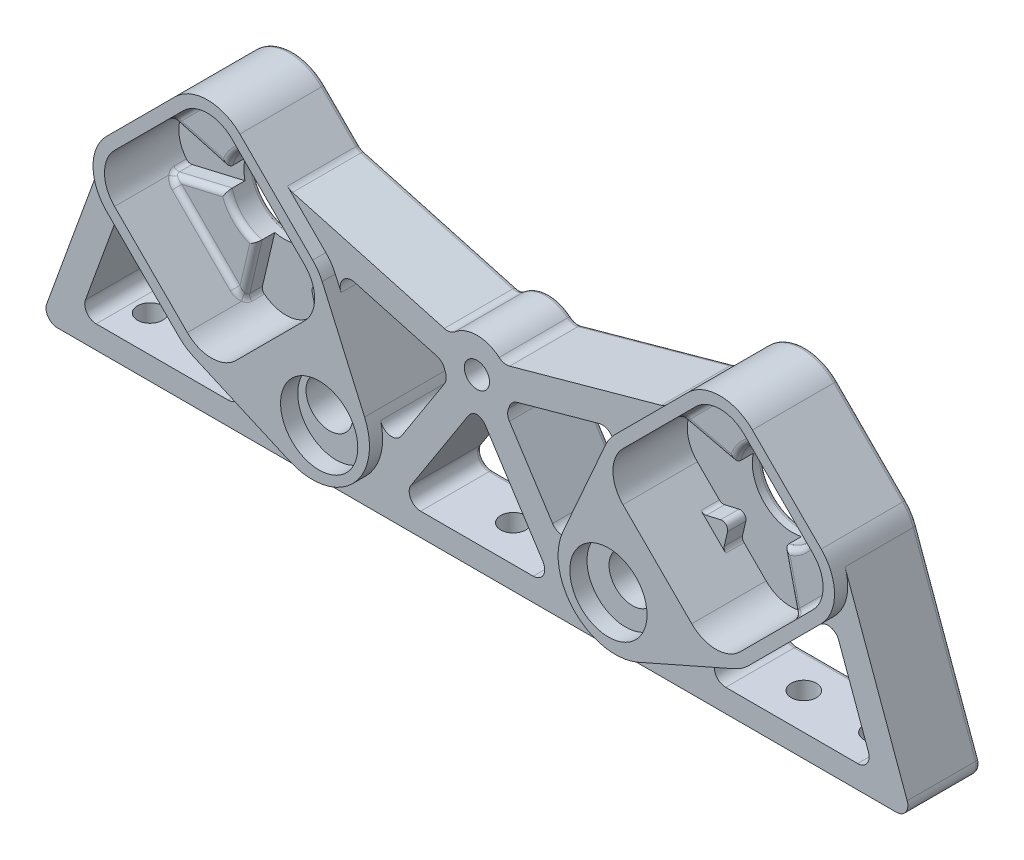
SolidWorks part; units mm, degrees
other "Markup1"
sketch "Sketch10" plane through (13.5539, 56.2954, 15) normal (-0.4315, 0.0322, 0.9016) x (0.8799, -0.2056, 0.4284)
ref_plane "Front Plane" through (0, 0, 0) normal (0, 0, 1) x (1, 0, 0)
ref_plane "Top Plane" through (0, 0, 0) normal (0, 1, 0) x (1, 0, 0)
ref_plane "Right Plane" through (0, 0, 0) normal (1, 0, 0) x (0, 0, -1)
sketch "Sketch1" plane through (0, 0, 0) normal (0, 0, 1) x (1, 0, 0)
  line L0 (0, 0) -> (60.4965, 0) construction
  circle A0 centre (0, 0) radius 25.4 construction
  circle A1 centre (44.45, 35.921) radius 31.75 construction
  circle A2 centre (133.35, 35.921) radius 31.75 construction
  circle A3 centre (177.8, 0) radius 25.4 construction
  circle A4 centre (222.25, 35.921) radius 31.75 construction
  circle A5 centre (311.15, 35.921) radius 31.75 construction
  circle A6 centre (355.6, 0) radius 25.4 construction
  circle A7 centre (0, 0) radius 50.8 construction
  circle A8 centre (355.6, 0) radius 50.8 construction
  circle A9 centre (177.8, 0) radius 50.8 construction
  circle A10 centre (88.9, 35.921) radius 12.7 construction
  circle A11 centre (266.7, 35.921) radius 12.7 construction
  point P20 (-50.8, 0)
  point P21 (406.4, 0)
  dimension "D1" = 50.8
  dimension "D2" = 63.5
  dimension "D4" = 101.6
  dimension "D5" = 25.4
  dimension "D6" = 25.4
  dimension "D3" = 355.6
  dimension "D7" = 177.8
  dimension "D8" = 177.8
  dimension "D9" = 457.2
  dimension "D10" = 44.45
sketch "Sketch2" plane through (0, 0, 0) normal (0, 0, 1) x (1, 0, 0)
  line L0 (-200000, 0) -> (200060.4965, 0) construction
  line L1 (-44.45, 6.35) -> (400.05, 6.35) construction
  line L2 (-44.45, 6.35) -> (-44.45, -19.05) construction
  line L3 (-44.45, -19.05) -> (400.05, -19.05) construction
  line L4 (400.05, 6.35) -> (400.05, -19.05) construction
  circle A0 centre (-38.1, 0) radius 2.25 construction
  circle A2 centre (-31.75, -6.35) radius 2.25 construction
  circle A3 centre (-25.4, 0) radius 2.25 construction
  circle A4 centre (-12.7, 0) radius 2.25 construction
  circle A5 centre (0, 0) radius 2.25 construction
  circle A6 centre (12.7, 0) radius 2.25 construction
  circle A7 centre (25.4, 0) radius 2.25 construction
  circle A8 centre (38.1, 0) radius 2.25 construction
  circle A9 centre (50.8, 0) radius 2.25 construction
  circle A10 centre (63.5, 0) radius 2.25 construction
  circle A11 centre (76.2, 0) radius 2.25 construction
  circle A12 centre (88.9, 0) radius 2.25 construction
  circle A13 centre (101.6, 0) radius 2.25 construction
  circle A14 centre (114.3, 0) radius 2.25 construction
  circle A15 centre (127, 0) radius 2.25 construction
  circle A16 centre (139.7, 0) radius 2.25 construction
  circle A17 centre (152.4, 0) radius 2.25 construction
  circle A18 centre (165.1, 0) radius 2.25 construction
  circle A19 centre (177.8, 0) radius 2.25 construction
  circle A20 centre (190.5, 0) radius 2.25 construction
  circle A21 centre (203.2, 0) radius 2.25 construction
  circle A22 centre (215.9, 0) radius 2.25 construction
  circle A23 centre (228.6, 0) radius 2.25 construction
  circle A24 centre (241.3, 0) radius 2.25 construction
  circle A25 centre (254, 0) radius 2.25 construction
  circle A26 centre (266.7, 0) radius 2.25 construction
  circle A27 centre (279.4, 0) radius 2.25 construction
  circle A28 centre (292.1, 0) radius 2.25 construction
  circle A29 centre (304.8, 0) radius 2.25 construction
  circle A30 centre (317.5, 0) radius 2.25 construction
  circle A31 centre (330.2, 0) radius 2.25 construction
  circle A32 centre (342.9, 0) radius 2.25 construction
  circle A33 centre (355.6, 0) radius 2.25 construction
  circle A34 centre (368.3, 0) radius 2.25 construction
  circle A35 centre (381, 0) radius 2.25 construction
  circle A36 centre (393.7, 0) radius 2.25 construction
  circle A37 centre (-25.4, -12.7) radius 2.25 construction
  circle A38 centre (-12.7, -12.7) radius 2.25 construction
  circle A39 centre (0, -12.7) radius 2.25 construction
  circle A40 centre (12.7, -12.7) radius 2.25 construction
  circle A41 centre (25.4, -12.7) radius 2.25 construction
  circle A42 centre (38.1, -12.7) radius 2.25 construction
  circle A43 centre (50.8, -12.7) radius 2.25 construction
  circle A44 centre (63.5, -12.7) radius 2.25 construction
  circle A45 centre (76.2, -12.7) radius 2.25 construction
  circle A46 centre (88.9, -12.7) radius 2.25 construction
  circle A47 centre (101.6, -12.7) radius 2.25 construction
  circle A48 centre (114.3, -12.7) radius 2.25 construction
  circle A49 centre (127, -12.7) radius 2.25 construction
  circle A50 centre (139.7, -12.7) radius 2.25 construction
  circle A51 centre (152.4, -12.7) radius 2.25 construction
  circle A52 centre (165.1, -12.7) radius 2.25 construction
  circle A53 centre (177.8, -12.7) radius 2.25 construction
  circle A54 centre (190.5, -12.7) radius 2.25 construction
  circle A55 centre (203.2, -12.7) radius 2.25 construction
  circle A56 centre (215.9, -12.7) radius 2.25 construction
  circle A57 centre (228.6, -12.7) radius 2.25 construction
  circle A58 centre (241.3, -12.7) radius 2.25 construction
  circle A59 centre (254, -12.7) radius 2.25 construction
  circle A60 centre (266.7, -12.7) radius 2.25 construction
  circle A61 centre (279.4, -12.7) radius 2.25 construction
  circle A62 centre (292.1, -12.7) radius 2.25 construction
  circle A63 centre (304.8, -12.7) radius 2.25 construction
  circle A64 centre (317.5, -12.7) radius 2.25 construction
  circle A65 centre (330.2, -12.7) radius 2.25 construction
  circle A66 centre (342.9, -12.7) radius 2.25 construction
  circle A67 centre (355.6, -12.7) radius 2.25 construction
  circle A68 centre (368.3, -12.7) radius 2.25 construction
  circle A69 centre (381, -12.7) radius 2.25 construction
  circle A70 centre (393.7, -12.7) radius 2.25 construction
  circle A71 centre (-38.1, -12.7) radius 2.25 construction
  circle A72 centre (-19.05, -6.35) radius 2.25 construction
  circle A73 centre (-6.35, -6.35) radius 2.25 construction
  circle A74 centre (6.35, -6.35) radius 2.25 construction
  circle A75 centre (19.05, -6.35) radius 2.25 construction
  circle A76 centre (31.75, -6.35) radius 2.25 construction
  circle A77 centre (44.45, -6.35) radius 2.25 construction
  circle A78 centre (57.15, -6.35) radius 2.25 construction
  circle A79 centre (69.85, -6.35) radius 2.25 construction
  circle A80 centre (82.55, -6.35) radius 2.25 construction
  circle A81 centre (95.25, -6.35) radius 2.25 construction
  circle A82 centre (107.95, -6.35) radius 2.25 construction
  circle A83 centre (120.65, -6.35) radius 2.25 construction
  circle A84 centre (133.35, -6.35) radius 2.25 construction
  circle A85 centre (146.05, -6.35) radius 2.25 construction
  circle A86 centre (158.75, -6.35) radius 2.25 construction
  circle A87 centre (171.45, -6.35) radius 2.25 construction
  circle A88 centre (184.15, -6.35) radius 2.25 construction
  circle A89 centre (196.85, -6.35) radius 2.25 construction
  circle A90 centre (209.55, -6.35) radius 2.25 construction
  circle A91 centre (222.25, -6.35) radius 2.25 construction
  circle A92 centre (234.95, -6.35) radius 2.25 construction
  circle A93 centre (247.65, -6.35) radius 2.25 construction
  circle A94 centre (260.35, -6.35) radius 2.25 construction
  circle A95 centre (273.05, -6.35) radius 2.25 construction
  circle A96 centre (285.75, -6.35) radius 2.25 construction
  circle A97 centre (298.45, -6.35) radius 2.25 construction
  circle A98 centre (311.15, -6.35) radius 2.25 construction
  circle A99 centre (323.85, -6.35) radius 2.25 construction
  circle A100 centre (336.55, -6.35) radius 2.25 construction
  circle A101 centre (349.25, -6.35) radius 2.25 construction
  circle A102 centre (361.95, -6.35) radius 2.25 construction
  circle A103 centre (374.65, -6.35) radius 2.25 construction
  circle A104 centre (387.35, -6.35) radius 2.25 construction
  dimension "D5" = 4.5
  dimension "D1" = 25.4
  dimension "D2" = 444.5
  dimension "D3" = 6.35
  dimension "D4" = 44.45
  dimension "D6" = 6.35
  dimension "D7" = 6.35
  dimension "D8" = 6.35
  dimension "D12" = 12.7
  dimension "D9" = 35
  dimension "D10" = 2
  dimension "D11" = 34
sketch "Sketch4" plane through (0, 0, 0) normal (0, 0, 1) x (1, 0, 0)
  line L0 (61.067, 39.8101) -> (48.3391, 52.538)
  line L1 (61.067, 31.3248) -> (49.0462, 19.304)
  line L2 (39.8538, 52.538) -> (27.833, 40.5172)
  line L3 (40.5609, 19.304) -> (27.833, 32.0319)
  line L4 (65.3097, 35.5675) -> (23.5903, 36.2746) construction
  line L5 (44.0964, 56.7807) -> (44.8036, 15.0614) construction
  line L6 (44.9803, 59.0788) -> (21.2923, 35.3907) construction
  line L7 (44.45, 35.921) -> (62.4105, 17.9605) construction
  line L8 (62.4105, 17.9605) -> (63.6126, 16.7584) construction
  line L9 (33.1363, 47.2347) -> (74.1485, 6.2225) construction
  line L10 (88.9, 35.921) -> (88.9, 9.7206) construction
  line L11 (44.9803, 59.0788) -> (85.9925, 18.0666) construction
  line L12 (21.2923, 35.3907) -> (62.3044, -5.6215) construction
  line L13 (85.9925, 18.0666) -> (62.3044, -5.6215) construction
  line L14 (132.8197, 59.0788) -> (156.5077, 35.3907) construction
  line L15 (156.5077, 35.3907) -> (115.4956, -5.6215) construction
  line L16 (132.8197, 59.0788) -> (91.8075, 18.0666) construction
  line L17 (91.8075, 18.0666) -> (115.4956, -5.6215) construction
  line L18 (137.9462, 52.538) -> (149.967, 40.5172)
  line L19 (137.2391, 19.304) -> (149.967, 32.0319)
  line L20 (116.733, 31.3248) -> (128.7538, 19.304)
  line L21 (116.733, 39.8101) -> (129.4609, 52.538)
  line L25 (-44.45, 6.35) -> (400.05, 6.35) construction
  circle A0 centre (44.45, 35.921) radius 7
  circle A1 centre (88.9, 35.921) radius 2.2
  arc A3 (61.067, 39.8101) -> (61.067, 31.3248) centre (56.8244, 35.5675) cw
  circle A4 centre (62.4105, 17.9605) radius 4.1
  circle A5 centre (63.6126, 16.7584) radius 6.75
  arc A6 (49.0462, 19.304) -> (40.5609, 19.304) centre (44.8036, 23.5467) cw
  arc A7 (27.833, 32.0319) -> (27.833, 40.5172) centre (32.0756, 36.2746) cw
  arc A8 (39.8538, 52.538) -> (48.3391, 52.538) centre (44.0964, 48.2954) cw
  circle A9 centre (115.3895, 17.9605) radius 4.1
  circle A10 centre (114.1874, 16.7584) radius 6.75
  circle A11 centre (133.35, 35.921) radius 7
  arc A12 (149.967, 32.0319) -> (149.967, 40.5172) centre (145.7244, 36.2746) ccw
  arc A13 (128.7538, 19.304) -> (137.2391, 19.304) centre (132.9964, 23.5467) ccw
  arc A14 (116.733, 39.8101) -> (116.733, 31.3248) centre (120.9756, 35.5675) ccw
  arc A15 (137.9462, 52.538) -> (129.4609, 52.538) centre (133.7036, 48.2954) ccw
  dimension "D1" = 4.4
  dimension "D2" = 14
  dimension "D7" = 13.5
  dimension "D8" = 8.2
  dimension "D9" = 6
  dimension "D3" = 29
  dimension "D4" = 30
  dimension "D5" = 10.4
  dimension "D6" = 1.7
  dimension "D10" = 58
  dimension "D11" = 33.5
  dimension "D12" = 16
  dimension "D13" = 45
sketch "Sketch6" plane through (0, 0, 0) normal (0, 0, 1) x (1, 0, 0)
  line L0 (72.4105, 10.35) -> (105.3895, 10.35)
  line L1 (88.9, 200035.921) -> (88.9, -199990.2794) construction
  line L2 (165.1, 6.35) -> (12.7, 6.35)
  line L3 (-44.45, 6.35) -> (400.05, 6.35) construction
  line L8 (40.5609, 19.304) -> (27.833, 32.0319) construction
  line L9 (61.067, 31.3248) -> (49.0462, 19.304) construction
  line L10 (61.067, 39.8101) -> (48.3391, 52.538) construction
  line L11 (39.8538, 52.538) -> (27.833, 40.5172) construction
  line L12 (40.5609, 19.304) -> (27.833, 32.0319) construction
  line L13 (61.067, 31.3248) -> (49.0462, 19.304) construction
  line L14 (61.067, 39.8101) -> (48.3391, 52.538) construction
  line L15 (62.4812, 41.2243) -> (49.7533, 53.9522)
  line L16 (39.8538, 52.538) -> (27.833, 40.5172) construction
  line L18 (38.4396, 53.9522) -> (26.4188, 41.9314)
  line L21 (39.1467, 17.8898) -> (26.4188, 30.6177)
  line L22 (71.5588, 21.9989) -> (64.143, 38.7982)
  line L23 (41.5728, 16.228) -> (58.3721, 8.8122)
  line L24 (54.8885, 10.35) -> (19.4716, 10.35)
  line L34 (19.4716, 10.35) -> (26.7206, 30.3159)
  line L37 (88.9, 35.921) -> (105.3895, 10.35) construction
  line L38 (12.7, 6.35) -> (24.5559, 39.0048)
  line L39 (88.9, 35.921) -> (44.0964, 48.2954) construction
  line L40 (84.308, 39.7829) -> (56.144, 47.5616)
  line L41 (63.1751, 40.4324) -> (82.9769, 34.9633)
  line L42 (88.9, 35.921) -> (133.7036, 48.2954) construction
  line L43 (137.9462, 52.538) -> (149.967, 40.5172) construction
  line L44 (88.9, 35.921) -> (72.4105, 10.35) construction
  line L45 (116.733, 39.8101) -> (129.4609, 52.538) construction
  line L46 (72.4105, 17.9605) -> (72.4105, 10.35)
  line L47 (72.4105, 14.963) -> (83.843, 32.692)
  line L48 (75.3852, 10.35) -> (88.0451, 29.9822)
  line L49 (116.733, 31.3248) -> (128.7538, 19.304) construction
  line L50 (88.9, 35.921) -> (88.9, 10.35) construction
  line L51 (137.2391, 19.304) -> (149.967, 32.0319) construction
  line L52 (102.4148, 10.35) -> (89.7549, 29.9822)
  line L53 (105.3895, 14.963) -> (93.957, 32.692)
  line L54 (105.3895, 17.9605) -> (105.3895, 10.35)
  line L55 (114.6249, 40.4324) -> (94.8231, 34.9633)
  line L56 (93.492, 39.7829) -> (121.656, 47.5616)
  line L57 (165.1, 6.35) -> (153.2441, 39.0048)
  line L58 (158.3284, 10.35) -> (151.0794, 30.3159)
  line L59 (122.9115, 10.35) -> (158.3284, 10.35)
  line L60 (136.2272, 16.228) -> (119.4279, 8.8122)
  line L61 (106.2412, 21.9989) -> (113.657, 38.7982)
  line L62 (138.6533, 17.8898) -> (151.3812, 30.6177)
  line L63 (139.3604, 53.9522) -> (151.3812, 41.9314)
  line L64 (115.3188, 41.2243) -> (128.0467, 53.9522)
  arc A0 (62.4812, 29.9106) -> (62.4812, 41.2243) centre (56.8244, 35.5675) ccw
  arc A1 (39.1467, 17.8898) -> (50.4604, 17.8898) centre (44.8036, 23.5467) ccw
  arc A2 (149.967, 40.5172) -> (149.967, 32.0319) centre (145.7244, 36.2746) cw construction
  arc A3 (129.4609, 52.538) -> (137.9462, 52.538) centre (133.7036, 48.2954) cw construction
  arc A4 (116.733, 31.3248) -> (116.733, 39.8101) centre (120.9756, 35.5675) cw construction
  arc A5 (137.2391, 19.304) -> (128.7538, 19.304) centre (132.9964, 23.5467) cw construction
  arc A12 (40.5609, 19.304) -> (49.0462, 19.304) centre (44.8036, 23.5467) ccw construction
  arc A14 (61.067, 31.3248) -> (61.067, 39.8101) centre (56.8244, 35.5675) ccw construction
  arc A15 (48.3391, 52.538) -> (39.8538, 52.538) centre (44.0964, 48.2954) ccw construction
  arc A16 (27.833, 40.5172) -> (27.833, 32.0319) centre (32.0756, 36.2746) ccw construction
  arc A17 (40.5609, 19.304) -> (49.0462, 19.304) centre (44.8036, 23.5467) ccw construction
  arc A18 (61.067, 31.3248) -> (61.067, 39.8101) centre (56.8244, 35.5675) ccw construction
  arc A19 (48.3391, 52.538) -> (39.8538, 52.538) centre (44.0964, 48.2954) ccw construction
  arc A20 (27.833, 40.5172) -> (27.833, 32.0319) centre (32.0756, 36.2746) ccw construction
  arc A21 (26.4188, 41.9314) -> (26.4188, 30.6177) centre (32.0756, 36.2746) ccw
  arc A22 (49.7533, 53.9522) -> (38.4396, 53.9522) centre (44.0964, 48.2954) ccw
  circle A25 centre (62.4105, 17.9605) radius 4.1 construction
  circle A26 centre (62.4105, 17.9605) radius 4.1
  circle A27 centre (115.3895, 17.9605) radius 10
  circle A28 centre (115.3895, 17.9605) radius 4.1
  arc A29 (128.0467, 53.9522) -> (139.3604, 53.9522) centre (133.7036, 48.2954) cw
  arc A30 (151.3812, 41.9314) -> (151.3812, 30.6177) centre (145.7244, 36.2746) cw
  arc A41 (138.6533, 17.8898) -> (127.3396, 17.8898) centre (132.9964, 23.5467) cw
  arc A42 (115.3188, 29.9106) -> (115.3188, 41.2243) centre (120.9756, 35.5675) cw
  circle A43 centre (62.4105, 17.9605) radius 10
  circle A44 centre (88.9, 35.921) radius 6
  point P62 (88.9, 10.35)
  point P86 (88.9, 6.35)
  dimension "D4" = 12
  dimension "D6" = 4
  dimension "D2" = 2
  dimension "D3" = 20
  dimension "D7" = 5
  dimension "D12" = 8
  dimension "D13" = 8
  dimension "D5" = 2
  dimension "D8" = 5
  dimension "D9" = 2.5
  dimension "D10" = 5
  dimension "D11" = 2.5
  dimension "D14" = 2
  dimension "D15" = 17
extrude "Boss-Extrude1" add sketch "Sketch6" along normal blind 12.7 contours A43 L22 A0 L15 A22 L18 A21 L21 A1 L23 | A43 L23 L24 L34 L21 A21 L38 L2 L57 A30 L62 L58 L59 L60 A27 L54 L0 L46 | A43 A26 | A44 L47 L46 L0 L48 | A44 L40 L15 A0 L41 | A44 | A44 L55 A42 L64 L56 | A44 L52 L0 L54 L53 | A27 A28 | A42 L61 A27 L60 A41 L62 A30 L63 A29 L64 region at (79.4718, 21.2253, 0) region at (73.8979, 8.7914, 0) region at (98.3282, 21.2253, 0) region at (88.9, 35.921, 0) region at (67.7158, 9.8194, 0) region at (45.2363, 35.1347, 0) region at (71.4188, 40.9045, 0) region at (105.8815, 19.9658, 0) region at (106.3812, 40.9045, 0) region at (132.5637, 35.1347, 0)
extrude "Boss-Extrude2" add sketch "Sketch6<3>" along normal blind 15 contours A42 L61 A27 L60 A41 L62 A30 L63 A29 L64 | A27 A28 | A43 A26 | A43 L22 A0 L15 A22 L18 A21 L21 A1 L23 region at (67.7158, 9.8194, 0) region at (45.2363, 35.1347, 0) region at (105.8815, 19.9658, 0) region at (132.5637, 35.1347, 0)
sketch "Sketch6<3>" plane through (0, 0, 0) normal (0, 0, 1) x (1, 0, 0) same geometry as "Sketch6"
extrude "Cut-Extrude1" cut sketch "Sketch4" against normal blind 13 from surface contours L18 A15 L21 A14 L20 A13 L19 A12 A11 | A8 L2 A7 L3 A6 L1 A3 L0 A0 region at (62.3047, 35.5675, 0) region at (143.5891, 46.1601, 0) starting at face at (129.7486, 32.3197, 15)
extrude "Cut-Extrude2" cut sketch "Sketch4<4>" along normal up to next contours A0 | A1 | A11 region at (44.45, 35.921, 0) region at (88.9, 35.921, 0) region at (133.35, 35.921, 0)
sketch "Sketch4<4>" plane through (0, 0, 0) normal (0, 0, 1) x (1, 0, 0) same geometry as "Sketch4"
extrude "Cut-Extrude3" cut sketch "Sketch4<5>" against normal blind 3 from surface contours A5 A4 | A10 A9 region at (57.0535, 16.7584, 0) region at (107.6283, 16.7584, 0) starting at face at (48.0514, 32.3197, 15)
sketch "Sketch4<5>" plane through (0, 0, 0) normal (0, 0, 1) x (1, 0, 0) same geometry as "Sketch4"
fillet "Fillet1" radius 2 24 edges at (56.144, 47.5616, 6.35) (121.656, 47.5616, 6.35) (93.492, 39.7829, 6.35) (84.308, 39.7829, 6.35) (165.1, 6.35, 6.35) (151.0794, 30.3159, 6.35) (158.3284, 10.35, 6.35) (122.9115, 10.35, 6.35) (114.6249, 40.4324, 6.35) (93.957, 32.692, 6.35) (94.8231, 34.9633, 6.35) (105.3895, 14.963, 6.35) (102.4148, 10.35, 6.35) (89.7549, 29.9822, 6.35) (88.0451, 29.9822, 6.35) (75.3852, 10.35, 6.35) (72.4105, 14.963, 6.35) (83.843, 32.692, 6.35) (82.9769, 34.9633, 6.35) (63.1751, 40.4324, 6.35) (12.7, 6.35, 6.35) (26.7206, 30.3159, 6.35) (19.4716, 10.35, 6.35) (54.8885, 10.35, 6.35)
sketch "Sketch7" plane through (0, 6.35, 0) normal (0, -1, 0) x (1, 0, 0)
  line L0 (15.5539, 12.7) -> (15.5539, 0) construction
  circle A0 centre (25.4, 6.35) radius 2.2
  circle A1 centre (38.1, 6.35) radius 2.2
  circle A2 centre (88.9, 6.35) radius 2.2
  circle A3 centre (139.7, 6.35) radius 2.2
  circle A4 centre (152.4, 6.35) radius 2.2
  point P0 (152.4, 0)
  point P2 (139.7, 0)
  point P4 (88.9, 0)
  point P6 (38.1, 0)
  point P8 (25.4, 0)
  point P24 (15.5539, 6.35)
  dimension "D1" = 4.4
extrude "Cut-Extrude4" cut sketch "Sketch7" against normal up to next
fillet "Fillet2" radius 0.75 66 edges at (51.45, 35.921, 0) (91.1, 35.921, 0) (105.9633, 21.2993, 0) (104.1152, 19.1284, 0) (98.3568, 25.869, 0) (94.2739, 32.629, 0) (94.5063, 33.7833, 0) (95.1014, 34.7993, 0) (103.1101, 37.2521, 0) (112.3251, 38.6114, 0) (109.4411, 29.2477, 0) (137.5172, 16.9465, 0) (143.7554, 22.9919, 0) (150.7054, 28.6323, 0) (154.7531, 20.1975, 0) (157.1123, 11.2022, 0) (143.9346, 10.35, 0) (130.4377, 11.9373, 0) (133.9071, 15.2038, 0) (88.0546, 29.6302, 0) (89.7454, 29.6302, 0) (95.4048, 21.2206, 0) (100.5014, 11.3929, 0) (88.9, 10.35, 0) (77.2986, 11.3929, 0) (82.3952, 21.2206, 0) (119.4895, 17.9605, 0) (66.5105, 17.9605, 0) (40.2828, 16.9465, 0) (43.8929, 15.2038, 0) (47.3623, 11.9373, 0) (33.8654, 10.35, 0) (20.6877, 11.2022, 0) (23.0469, 20.1975, 0) (27.0946, 28.6323, 0) (34.0446, 22.9919, 0) (152.4732, 40.5703, 0) (145.3708, 47.9418, 0) (133.7036, 56.2954, 0) (125.0379, 50.9435, 0) (121.6216, 47.6207, 0) (107.8787, 43.7564, 0) (93.6466, 40.0665, 0) (88.9, 41.921, 0) (84.1534, 40.0665, 0) (69.9213, 43.7564, 0) (56.1784, 47.6207, 0) (52.7621, 50.9435, 0) (44.0964, 56.2954, 0) (32.4292, 47.9418, 0) (25.3268, 40.5703, 0) (19.1149, 24.0186, 0) (13.916, 7.2022, 0) (88.9, 6.35, 0) (163.884, 7.2022, 0) (158.6851, 24.0186, 0) (82.6986, 34.7993, 0) (83.2937, 33.7833, 0) (83.5261, 32.629, 0) (79.4432, 25.869, 0) (73.6848, 19.1284, 0) (71.8367, 21.2993, 0) (68.3589, 29.2477, 0) (65.4749, 38.6114, 0) (74.6899, 37.2521, 0) (140.35, 35.921, 0)
sketch "Sketch9" plane through (0, 0, 2) normal (0, 0, 1) x (1, 0, 0)
  line L0 (27.833, 32.0319) -> (37.6342, 34.3258)
  line L1 (40.5609, 19.304) -> (42.8548, 29.1052)
  line L2 (48.3391, 52.538) -> (46.0452, 42.7368)
  line L3 (61.067, 39.8101) -> (51.2658, 37.5162)
  line L4 (61.067, 39.8101) -> (48.3391, 52.538)
  line L5 (39.8538, 52.538) -> (27.833, 40.5172)
  line L6 (27.833, 32.0319) -> (40.5609, 19.304)
  line L7 (49.0462, 19.304) -> (61.067, 31.3248)
  line L8 (61.067, 39.8101) -> (48.3391, 52.538)
  line L9 (39.8538, 52.538) -> (27.833, 40.5172)
  line L10 (27.833, 32.0319) -> (40.5609, 19.304)
  line L11 (49.0462, 19.304) -> (61.067, 31.3248) construction
  line L12 (27.833, 40.5172) -> (37.7033, 37.7871)
  line L13 (39.8538, 52.538) -> (42.5839, 42.6677)
  line L14 (88.9, 35.921) -> (88.9, 10.35) construction
  line L15 (55.0566, 25.3144) -> (52.2282, 28.1428) construction
  line L16 (149.967, 32.0319) -> (137.2391, 19.304)
  line L17 (116.733, 39.8101) -> (129.4609, 52.538)
  line L18 (137.9462, 52.538) -> (149.967, 40.5172)
  line L19 (137.9462, 52.538) -> (135.2161, 42.6677)
  line L20 (137.2391, 19.304) -> (134.9452, 29.1052)
  line L21 (149.967, 32.0319) -> (140.1658, 34.3258)
  line L22 (149.967, 40.5172) -> (140.0967, 37.7871)
  line L23 (116.733, 39.8101) -> (126.5342, 37.5162)
  line L24 (129.4609, 52.538) -> (131.7548, 42.7368)
  line L25 (52.2282, 28.1428) -> (53.2888, 23.5467)
  line L26 (52.2282, 28.1428) -> (56.8244, 27.0822)
  line L27 (128.7538, 19.304) -> (116.733, 31.3248) construction
  line L28 (125.5718, 28.1428) -> (124.5112, 23.5467)
  line L29 (125.5718, 28.1428) -> (120.9756, 27.0822)
  line L30 (120.9756, 27.0822) -> (124.5112, 23.5467)
  circle A0 centre (44.45, 35.921) radius 7 construction
  circle A1 centre (44.45, 35.921) radius 7
  circle A2 centre (133.35, 35.921) radius 7
  arc A4 (48.3391, 52.538) -> (39.8538, 52.538) centre (44.0964, 48.2954) ccw
  arc A5 (27.833, 40.5172) -> (27.833, 32.0319) centre (32.0756, 36.2746) ccw
  arc A6 (40.5609, 19.304) -> (49.0462, 19.304) centre (44.8036, 23.5467) ccw
  arc A7 (61.067, 31.3248) -> (61.067, 39.8101) centre (56.8244, 35.5675) ccw
  arc A8 (48.3391, 52.538) -> (39.8538, 52.538) centre (44.0964, 48.2954) ccw
  arc A9 (27.833, 40.5172) -> (27.833, 32.0319) centre (32.0756, 36.2746) ccw
  arc A10 (40.5609, 19.304) -> (49.0462, 19.304) centre (44.8036, 23.5467) ccw
  arc A11 (61.067, 31.3248) -> (61.067, 39.8101) centre (56.8244, 35.5675) ccw
  point P22 (88.9, 35.921)
  circle M13 centre (44.45, 35.921) radius 7
  line M14 (61.067, 39.8101) -> (48.3391, 52.538)
  line M16 (39.8538, 52.538) -> (27.833, 40.5172)
  line M18 (27.833, 32.0319) -> (40.5609, 19.304)
  line M20 (49.0462, 19.304) -> (61.067, 31.3248)
  dimension "D2" = 5
  dimension "D3" = 2.5
  dimension "D4" = 4
  dimension "D1" = 0
extrude "Boss-Extrude3" add sketch "Sketch9" along normal blind 3.2 contours L1 L0 M18 M13 | L13 L12 M16 M13 | L3 L2 M14 M13 | L26 L25 M20 | L21 A2 L20 L16 | L19 A2 L22 L18 | L23 A2 L24 L17 | L30 L28 L29 region at (36.6388, 28.1098, 2) region at (36.4115, 43.9596, 2) region at (54.1138, 26.2572, 2) region at (52.2612, 43.7322, 2) region at (141.1612, 28.1098, 2) region at (125.5388, 43.7322, 2) region at (141.3885, 43.9596, 2)
fillet "Fillet3" radius 1 24 edges at (32.7336, 33.1789, 5.2) (41.7079, 24.2046, 5.2) (56.1664, 38.6632, 5.2) (47.1921, 47.6374, 5.2) (41.2189, 47.6029, 5.2) (32.7682, 39.1522, 5.2) (39.5003, 30.9713, 5.2) (49.3997, 40.8708, 5.2) (39.5003, 40.8708, 5.2) (138.2997, 30.9713, 5.2) (136.0921, 24.2046, 5.2) (145.0664, 33.1789, 5.2) (145.0318, 39.1522, 5.2) (138.2997, 40.8708, 5.2) (128.4003, 40.8708, 5.2) (121.6336, 38.6632, 5.2) (130.6079, 47.6374, 5.2) (136.5811, 47.6029, 5.2) (56.8244, 27.0822, 3.6) (53.2888, 23.5467, 3.6) (124.5112, 23.5467, 3.6) (120.9756, 27.0822, 3.6) (125.5718, 28.1428, 3.6) (52.2282, 28.1428, 3.6)
fillet "Fillet4" radius 1 30 edges at (27.833, 32.0319, 3.1) (28.0767, 31.7882, 4.9071) (40.5609, 19.304, 3.1) (40.3172, 19.5478, 4.9071) (61.067, 39.8101, 3.1) (60.8233, 40.0539, 4.9071) (48.3391, 52.538, 3.1) (48.5828, 52.2943, 4.9071) (39.8538, 52.538, 3.1) (39.6158, 52.3, 4.9071) (27.833, 40.5172, 3.1) (28.071, 40.7553, 4.9071) (34.197, 25.668, 5.2) (54.703, 46.1741, 5.2) (33.8434, 46.5276, 5.2) (149.967, 32.0319, 3.1) (149.7233, 31.7882, 4.9071) (137.2391, 19.304, 3.1) (137.4828, 19.5478, 4.9071) (137.9462, 52.538, 3.1) (138.1842, 52.3, 4.9071) (149.967, 40.5172, 3.1) (149.729, 40.7553, 4.9071) (116.733, 39.8101, 3.1) (116.9767, 40.0539, 4.9071) (129.4609, 52.538, 3.1) (129.2172, 52.2943, 4.9071) (143.603, 25.668, 5.2) (143.9566, 46.5276, 5.2) (123.097, 46.1741, 5.2)
